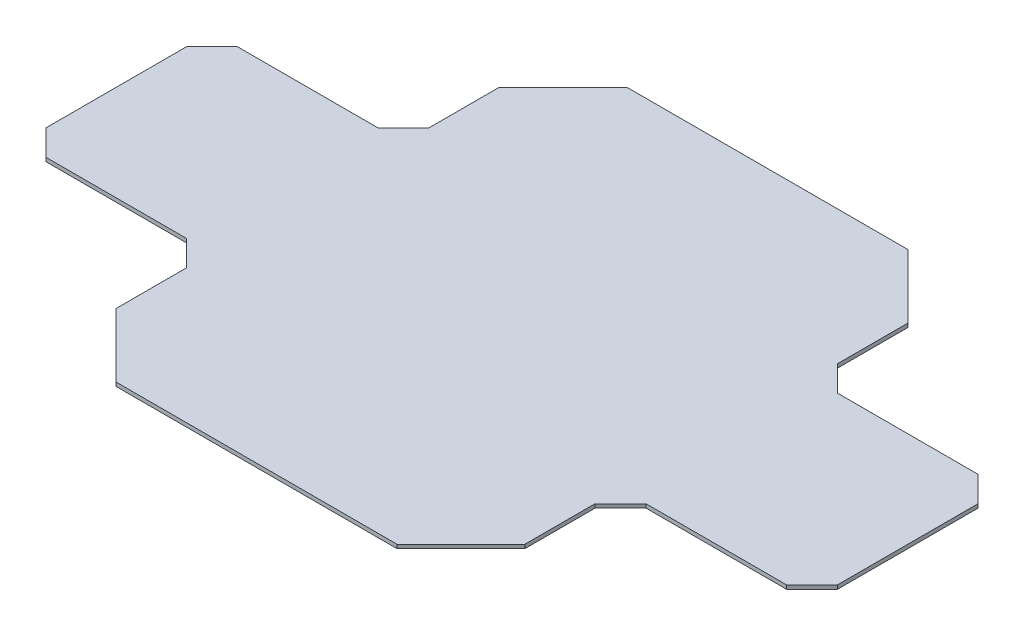
SolidWorks part; units mm, degrees
ref_plane "前视基准面" through (0, 0, 0) normal (0, 0, 1) x (1, 0, 0)
ref_plane "上视基准面" through (0, 0, 0) normal (0, 1, 0) x (1, 0, 0)
ref_plane "右视基准面" through (0, 0, 0) normal (1, 0, 0) x (0, 0, -1)
sketch "草图1" plane through (0, 0, 0) normal (0, 1, 0) x (1, 0, 0)
  line L0 (0, 0) -> (160, -38.7097) construction
  line L1 (-260, 200) -> (260, 200) construction
  line L2 (-260, 200) -> (-260, -200) construction
  line L3 (-260, -200) -> (260, -200) construction
  line L4 (260, 200) -> (260, -200) construction
  line L5 (-260, 200) -> (-160, 123.0769) construction
  line L6 (-260, -200) -> (-160, -123.0769) construction
  line L7 (-310, -75) -> (-160, -75)
  line L8 (-310, -75) -> (-310, 75)
  line L9 (-310, 75) -> (-160, 75)
  line L10 (310, -75) -> (310, 75)
  line L11 (-310, -75) -> (160, 38.7097) construction
  line L12 (-310, 75) -> (-160, 38.7097) construction
  line L13 (-160, -200) -> (160, -200)
  line L14 (-160, -200) -> (-160, -75)
  line L15 (-160, 200) -> (160, 200)
  line L16 (160, -200) -> (160, -75)
  line L17 (-60, -75) -> (0, 0) construction
  line L18 (0, 0) -> (60, -75) construction
  line L19 (-160, 75) -> (-160, 200)
  line L22 (160, 75) -> (310, 75)
  line L24 (97.5, 75) -> (260, 200) construction
  line L25 (160, 75) -> (160, 200)
  line L26 (260, 62.9032) -> (310, 75) construction
  line L27 (260, -62.9032) -> (310, -75) construction
  line L28 (160, -75) -> (310, -75)
  line L29 (160, -123.0769) -> (260, -200) construction
  point P0 (0, 0)
  point P6 (0, 0)
  point P11 (0, 0)
  dimension "D1" = 520
  dimension "D2" = 400
  dimension "D3" = 50
  dimension "D4" = 125
  dimension "D5" = 100
extrude "凸台-拉伸1" add sketch "草图1" along normal blind 3
chamfer "倒角1" distance 20 angle 45 8 edges at (-160, 1.5, -75) (-310, 1.5, -75) (-310, 1.5, 75) (-160, 1.5, 75) (160, 1.5, 75) (160, 1.5, -75) (310, 1.5, 75) (310, 1.5, -75)
chamfer "倒角2" distance 50 angle 45 4 edges at (160, 1.5, 200) (-160, 1.5, 200) (160, 1.5, -200) (-160, 1.5, -200)
